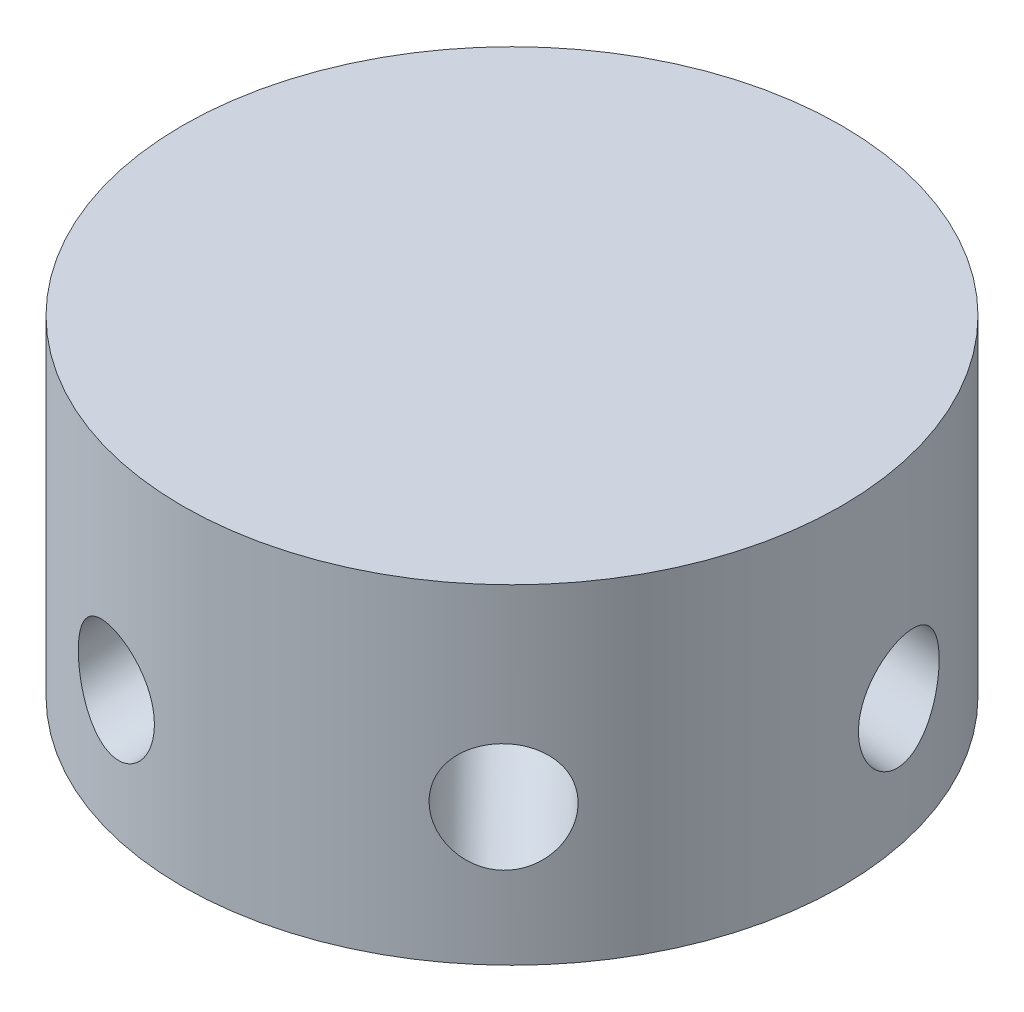
SolidWorks part; units mm, degrees
ref_plane "Front Plane" through (0, 0, 0) normal (0, 0, 1) x (1, 0, 0)
ref_plane "Top Plane" through (0, 0, 0) normal (0, 1, 0) x (1, 0, 0)
ref_plane "Right Plane" through (0, 0, 0) normal (1, 0, 0) x (0, 0, -1)
sketch "Sketch1" plane through (0, 0, 0) normal (0, 1, 0) x (1, 0, 0)
  circle A0 centre (0, 0) radius 10
  dimension "D1" = 20
extrude "base" add sketch "Sketch1" along normal blind 3 and the other way blind 7
ref_axis "6hubaxis" through (0, 5.5, 0) along (0, -1, 0)
ref_plane "Plane1" through (2.6705, -1.0931, 2.7701) normal (-0.6676, 0.2733, -0.6925) x (-0.6559, 0.2243, 0.7208)
sketch "Sketch2" plane through (2.6705, -1.0931, 2.7701) normal (-0.6676, 0.2733, -0.6925) x (-0.6559, 0.2243, 0.7208)
  circle A0 centre (0, 0) radius 1.5 construction
  circle A1 centre (0, 0) radius 1.5 construction
  circle A2 centre (0, 0) radius 1.6
  dimension "D1" = 3.2
extrude "hole1" cut sketch "Sketch2" against normal through all
pattern_circular "hole1mirror" count 2 over 360 about axis through (0, 5.5, 0) along (0, -1, 0) of "hole1"
ref_plane "Plane2" through (-0.9417, -1.2361, 3.6858) normal (0.2354, 0.309, -0.9215) x (-0.9719, 0.0738, -0.2235)
sketch "Sketch3" plane through (-0.9417, -1.2361, 3.6858) normal (0.2354, 0.309, -0.9215) x (-0.9719, 0.0738, -0.2235)
  circle A0 centre (0, 0) radius 1.5 construction
  circle A1 centre (0, 0) radius 1.5 construction
  circle A2 centre (0, 0) radius 1.6
  dimension "D1" = 3.2
extrude "hole2" cut sketch "Sketch3" against normal through all
pattern_circular "hole2mirror" count 2 over 360 about axis through (0, 5.5, 0) along (0, -1, 0) of "hole2"
ref_plane "Plane3" through (-3.7178, -1.2361, 0.8061) normal (0.9295, 0.309, -0.2015) x (-0.1912, -0.0636, -0.9795)
sketch "Sketch4" plane through (-3.7178, -1.2361, 0.8061) normal (0.9295, 0.309, -0.2015) x (-0.1912, -0.0636, -0.9795)
  circle A0 centre (0, 0) radius 1.5 construction
  circle A1 centre (0, 0) radius 1.5 construction
  circle A2 centre (0, 0) radius 1.6
  dimension "D1" = 3.2
extrude "hole3" cut sketch "Sketch4" against normal through all
pattern_circular "hole3mirror" count 2 over 360 about axis through (0, 5.5, 0) along (0, -1, 0) of "hole3"
